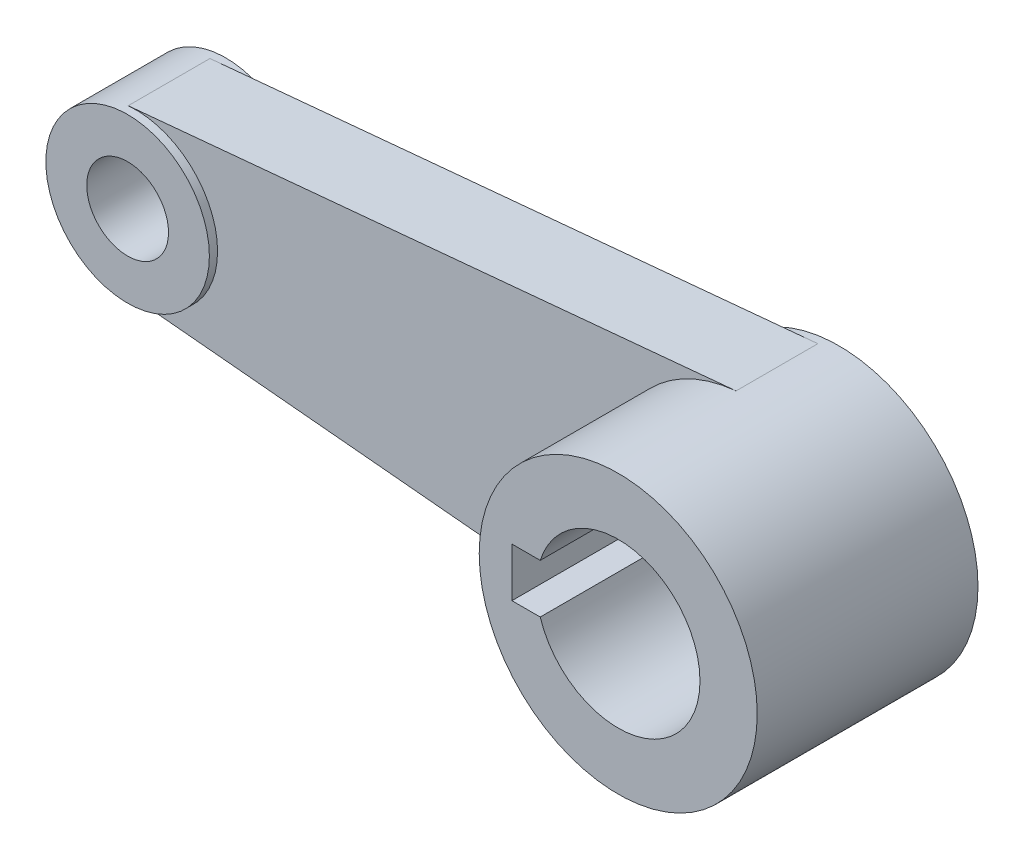
SolidWorks part; units mm, degrees
ref_plane "Piano frontale" through (0, 0, 0) normal (0, 0, 1) x (1, 0, 0)
ref_plane "Piano superiore" through (0, 0, 0) normal (0, 1, 0) x (1, 0, 0)
ref_plane "Piano destro" through (0, 0, 0) normal (1, 0, 0) x (0, 0, -1)
sketch "Schizzo2" plane through (0, 0, 0) normal (0, 0, 1) x (1, 0, 0)
  line L0 (-75, 0) -> (0, 0) construction
  line L1 (-75.9333, 9.9563) -> (-1.5867, 16.9258)
  line L2 (-75.9333, -9.9563) -> (-1.5867, -16.9258)
  line L4 (-13, 3) -> (-9.5394, 3)
  line L5 (-13, 3) -> (-13, -3)
  line L6 (-13, -3) -> (-9.5394, -3)
  circle A0 centre (0, 0) radius 17
  circle A1 centre (-75, 0) radius 10
  arc A2 (-9.5394, -3) -> (-9.5394, 3) centre (0, 0) ccw
  point P8 (-9.884, 5.7783)
  dimension "D1" = 20
  dimension "D2" = 10
  dimension "D3" = 34
  dimension "D4" = 6
  dimension "D5" = 23
  dimension "D6" = 75
extrude "Estrusione-Estrusione1" add sketch "Schizzo2" along normal mid plane 12 contours A1 region at (-75, 0, 0)
extrude "Estrusione-Estrusione2" add sketch "Schizzo2<3>" along normal blind 21 and the other way blind 6 separate body contours A0 L5 L4 A2 L6 region at (11.1224, 12.2138, 0)
sketch "Schizzo2<3>" plane through (0, 0, 0) normal (0, 0, 1) x (1, 0, 0) same geometry as "Schizzo2"
extrude "Estrusione-Estrusione3" add sketch "Schizzo2<4>" along normal mid plane 10 contours A1 L0 A0 L1 | L0 A1 L2 A0 region at (-38.8614, 7.1372, 0) region at (-38.8614, -7.1372, 0)
sketch "Schizzo2<4>" plane through (0, 0, 0) normal (0, 0, 1) x (1, 0, 0) same geometry as "Schizzo2"
hole_wizard "Foro Ø10.0 (10)-1" positions "Schizzo3" profile "Schizzo4" hole size "Ø10.0" standard "ISO" end condition through all
sketch "Schizzo3" plane through (0, 0, 6) normal (0, 0, 1) x (1, 0, 0)
  point P0 (-75, 0)
sketch "Schizzo4" plane through (-75, 0, 6) normal (1, 0, 0) x (0, -1, 0)
  line L0 (0, 0) -> (0, 12)
  line L1 (0, 12) -> (5, 12)
  line L2 (5, 12) -> (5, 0)
  line L5 (5, 0) -> (0, 0)
  line L11 (0, -6.35) -> (0, 107.95) construction
  dimension "Thru Hole Dia." = 10
  dimension "Thru Hole Depth" = 12
